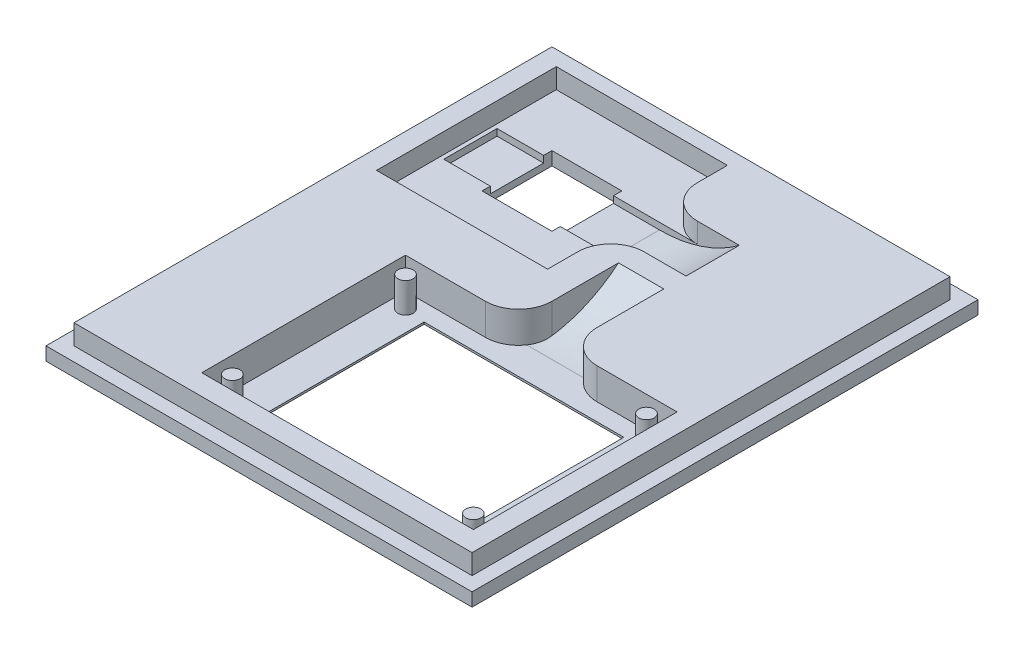
SolidWorks part; units mm, degrees
ref_plane "Front Plane" through (0, 0, 0) normal (0, 0, 1) x (1, 0, 0)
ref_plane "Top Plane" through (0, 0, 0) normal (0, 1, 0) x (1, 0, 0)
ref_plane "Right Plane" through (0, 0, 0) normal (1, 0, 0) x (0, 0, -1)
sketch "Sketch1" plane through (0, 0, 0) normal (0, 1, 0) x (1, 0, 0)
  line L1 (-32, 38) -> (32, 38)
  line L2 (-32, 38) -> (-32, -38)
  line L3 (-32, -38) -> (32, -38)
  line L4 (32, 38) -> (32, -38)
  line L5 (-32, 38) -> (32, -38) construction
  line L6 (-32, -38) -> (32, 38) construction
  point P0 (0, 0)
  dimension "D1" = 76
  dimension "D2" = 64
extrude "Top" add sketch "Sketch1" along normal blind 2
sketch "Sketch2" plane through (0, 2, 0) normal (0, 1, 0) x (1, 0, 0)
  line L0 (32, -38) -> (32, 38) construction
  line L1 (-29.9, 35.9) -> (29.9, 35.9)
  line L2 (-29.9, 35.9) -> (-29.9, -35.9)
  line L3 (-29.9, -35.9) -> (29.9, -35.9)
  line L4 (29.9, 35.9) -> (29.9, -35.9)
  line L5 (-29.9, 35.9) -> (29.9, -35.9) construction
  line L6 (-29.9, -35.9) -> (29.9, 35.9) construction
  line L7 (32, 38) -> (-32, 38) construction
  point P0 (0, 0)
  dimension "D1" = 2.1
  dimension "D2" = 2.1
extrude "Boss-Extrude2" add sketch "Sketch2" along normal blind 3
sketch "Sketch3" plane through (0, 5, 0) normal (0, 1, 0) x (1, 0, 0)
  line L1 (-19.4, 25.4) -> (-8.9, 25.4)
  line L2 (-19.4, 25.4) -> (-19.4, 14.9)
  line L3 (-19.4, 14.9) -> (-8.9, 14.9)
  line L4 (-8.9, 25.4) -> (-8.9, 14.9)
  line L5 (-19.4, 25.4) -> (-8.9, 14.9) construction
  line L6 (-19.4, 14.9) -> (-8.9, 25.4) construction
  line L8 (29.9, 35.9) -> (-29.9, 35.9) construction
  line L9 (-29.9, 35.9) -> (-29.9, -35.9) construction
  point P0 (-14.15, 20.15)
  dimension "D1" = 10.5
  dimension "D2" = 10.5
  dimension "D3" = 10.5
extrude "Cut-Extrude1" cut sketch "Sketch3" against normal blind 6
sketch "Sketch10" plane through (0, 5, 0) normal (0, 1, 0) x (1, 0, 0)
  line L0 (-14.15, 25.4) -> (-14.15, 14.9) construction
  line L1 (-8.9, 25.4) -> (-19.4, 25.4) construction
  line L2 (-19.4, 14.9) -> (-8.9, 14.9) construction
  line L4 (-27, 33.65) -> (-1.3, 33.65)
  line L5 (-27, 33.65) -> (-27, 6.65)
  line L6 (-27, 6.65) -> (-1.3, 6.65)
  line L7 (-1.3, 33.65) -> (-1.3, 6.65)
  line L8 (-27, 33.65) -> (-1.3, 6.65) construction
  line L9 (-27, 6.65) -> (-1.3, 33.65) construction
  point P6 (-14.15, 20.15)
  dimension "D1" = 27
  dimension "D2" = 25.7
extrude "Cut-Extrude8" cut sketch "Sketch10" against normal blind 3
sketch "Sketch11" plane through (0, 2, 0) normal (0, 1, 0) x (1, 0, 0)
  line L1 (-26.4, 24.15) -> (-19.4, 24.15)
  line L2 (-26.4, 24.15) -> (-26.4, 16.15)
  line L3 (-26.4, 16.15) -> (-19.4, 16.15)
  line L4 (-19.4, 24.15) -> (-19.4, 16.15)
  line L5 (-8.9, 24.15) -> (-1.9, 24.15)
  line L6 (-8.9, 24.15) -> (-8.9, 16.15)
  line L7 (-8.9, 16.15) -> (-1.9, 16.15)
  line L8 (-1.9, 24.15) -> (-1.9, 16.15)
  line L10 (-8.9, 25.4) -> (-8.9, 14.9) construction
  line L11 (-19.4, 14.9) -> (-19.4, 25.4) construction
  line L12 (-8.9, 20.15) -> (-19.4, 20.15) construction
  point P14 (-19.4, 20.15)
  dimension "D1" = 7
  dimension "D2" = 8
extrude "Cut-Extrude9" cut sketch "Sketch11" against normal blind 1
sketch "Sketch6" plane through (0, 5, 0) normal (0, 1, 0) x (1, 0, 0)
  line L0 (-29.9, -35.9) -> (29.9, -35.9) construction
  line L1 (-8.4, -4.8) -> (21.6, -4.8)
  line L2 (-8.4, -4.8) -> (-8.4, -30.2)
  line L3 (-8.4, -30.2) -> (21.6, -30.2)
  line L4 (21.6, -4.8) -> (21.6, -30.2)
  line L5 (-8.4, -4.8) -> (21.6, -30.2) construction
  line L6 (-8.4, -30.2) -> (21.6, -4.8) construction
  line L7 (26.9, -2.1) -> (-13.7, -2.1) construction
  line L8 (26.9, -2.1) -> (26.9, -32.9) construction
  line L9 (26.9, -32.9) -> (-13.7, -32.9) construction
  line L10 (-13.7, -2.1) -> (-13.7, -32.9) construction
  line L11 (26.9, -2.1) -> (-13.7, -32.9) construction
  line L12 (26.9, -32.9) -> (-13.7, -2.1) construction
  line L14 (29.9, -35.9) -> (29.9, 35.9) construction
  point P0 (6.6, -17.5)
  point P5 (6.6, -17.5)
  dimension "D1" = 25.4
  dimension "D2" = 30
  dimension "D3" = 40.6
  dimension "D4" = 30.8
  dimension "D5" = 3
  dimension "D6" = 3
extrude "Cut-Extrude4" cut sketch "Sketch6" against normal blind 6
sketch "Sketch7" plane through (0, 5, 0) normal (0, 1, 0) x (1, 0, 0)
  line L0 (6.6, -4.8) -> (6.6, -30.2) construction
  line L1 (21.6, -4.8) -> (-8.4, -4.8) construction
  line L2 (-8.4, -30.2) -> (21.6, -30.2) construction
  line L3 (-13.8, -17.5) -> (27, -17.5) construction
  line L4 (-13.8, -2.2) -> (27, -2.2) construction
  line L5 (-13.8, -2.2) -> (-13.8, -32.8) construction
  line L6 (-13.8, -32.8) -> (27, -32.8) construction
  line L7 (27, -2.2) -> (27, -32.8) construction
  line L8 (-13.8, -2.2) -> (27, -32.8) construction
  line L9 (-13.8, -32.8) -> (27, -2.2) construction
  line L14 (-13.8, -2.2) -> (-11.5, -2.2) construction
  line L15 (-13.8, -2.2) -> (-13.8, -4.5) construction
  line L16 (-13.8, -4.5) -> (-11.5, -4.5) construction
  line L17 (-11.5, -2.2) -> (-11.5, -4.5) construction
  circle A0 centre (-11.5, -4.5) radius 1.15
  circle A1 centre (-11.5, -30.5) radius 1.15
  circle A2 centre (24.7, -30.5) radius 1.15
  circle A3 centre (24.7, -4.5) radius 1.15
  point P6 (6.6, -17.5)
  dimension "D4" = 2.3
  dimension "D1" = 30.6
  dimension "D2" = 40.8
  dimension "D3" = 2.3
extrude "Boss-Extrude3" add sketch "Sketch7" against normal blind 4.7
sketch "Sketch8" plane through (0, 5, 0) normal (0, 1, 0) x (1, 0, 0)
  line L0 (6.6, -4.8) -> (6.6, -30.2) construction
  line L1 (21.6, -4.8) -> (-8.4, -4.8) construction
  line L2 (-8.4, -30.2) -> (21.6, -30.2) construction
  line L4 (-13.8, -2.2) -> (27, -2.2)
  line L5 (-13.8, -2.2) -> (-13.8, -32.8)
  line L6 (-13.8, -32.8) -> (27, -32.8)
  line L7 (27, -2.2) -> (27, -32.8)
  line L8 (-13.8, -2.2) -> (27, -32.8) construction
  line L9 (-13.8, -32.8) -> (27, -2.2) construction
  point P6 (6.6, -17.5)
  dimension "D1" = 30.6
  dimension "D2" = 40.8
extrude "Cut-Extrude6" cut sketch "Sketch8" against normal blind 4.7
sketch "Sketch9" plane through (0, 5, 0) normal (0, 1, 0) x (1, 0, 0)
  line L0 (-13.8, -2.2) -> (-13.8, -32.8) construction
  line L1 (3.2, 12.8) -> (10, 12.8)
  line L2 (3.2, 12.8) -> (3.2, -2.2)
  line L3 (3.2, -2.2) -> (10, -2.2)
  line L4 (10, 12.8) -> (10, -2.2)
  line L5 (27, -32.8) -> (27, -2.2) construction
  line L6 (27, -2.2) -> (-13.8, -2.2) construction
  dimension "D1" = 17
  dimension "D2" = 17
  dimension "D3" = 15
  dimension "D4" = 0
extrude "Cut-Extrude7" cut sketch "Sketch9" against normal blind 4.7
fillet "Fillet2" radius 20 1 edges at (6.6, 0.3, -12.8)
fillet "Fillet3" radius 5 2 edges at (10, 2.65, 2.2) (3.2, 2.65, 2.2)
sketch "Sketch14" plane through (0, 0.3, 0) normal (0, 1, 0) x (1, 0, 0)
  line L0 (6.6, -4.8) -> (6.6, -30.2) construction
  line L1 (-8.4, -4.8) -> (21.6, -4.8) construction
  line L2 (21.6, -30.2) -> (-8.4, -30.2) construction
  line L3 (-8.4, -17.5) -> (21.6, -17.5) construction
  line L4 (-8.4, -30.2) -> (-8.4, -4.8) construction
  line L5 (21.6, -4.8) -> (21.6, -30.2) construction
  line L7 (-13.8, -2.2) -> (-11.5, -2.2) construction
  line L8 (-13.8, -2.2) -> (-13.8, -4.5) construction
  line L9 (-13.8, -4.5) -> (-11.5, -4.5) construction
  line L10 (-11.5, -2.2) -> (-11.5, -4.5) construction
  circle A0 centre (-11.5, -4.5) radius 1.15
  circle A1 centre (24.7, -4.5) radius 1.15
  circle A2 centre (24.7, -30.5) radius 1.15
  circle A3 centre (-11.5, -30.5) radius 1.15
  dimension "D1" = 2.3
extrude "Boss-Extrude4" add sketch "Sketch14" along normal blind 4.5
sketch "Sketch12" plane through (0, 5, 0) normal (0, 1, 0) x (1, 0, 0)
  line L0 (-1.9, 24.15) -> (-8.9, 24.15) construction
  line L1 (-1.9, 24.15) -> (10, 24.15)
  line L2 (-1.9, 24.15) -> (-1.9, 16.15)
  line L3 (-1.9, 16.15) -> (10, 16.15)
  line L4 (10, 24.15) -> (10, 16.15)
  line L5 (-8.9, 16.15) -> (-1.9, 16.15) construction
  line L6 (-1.9, 16.15) -> (-1.9, 24.15) construction
  line L8 (10, 2.8) -> (10, 12.8) construction
extrude "Cut-Extrude10" cut sketch "Sketch12" against normal blind 4
fillet "Fillet4" radius 20 1 edges at (10, 1, -20.15)
fillet "Fillet5" radius 5 2 edges at (-1.3, 3.5, -16.15) (-1.3, 3.5, -24.15)
